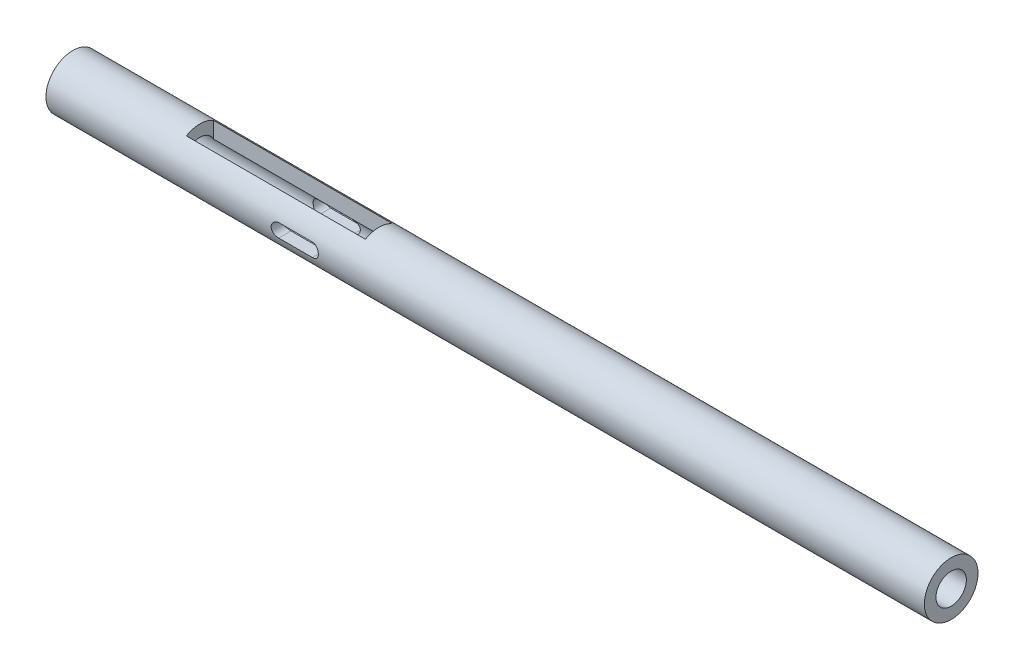
SolidWorks part; units mm, degrees
ref_plane "Front Plane" through (0, 0, 0) normal (0, 0, 1) x (1, 0, 0)
ref_plane "Top Plane" through (0, 0, 0) normal (0, 1, 0) x (1, 0, 0)
ref_plane "Right Plane" through (0, 0, 0) normal (1, 0, 0) x (0, 0, -1)
ref_axis "Axis1" through (105.6, 0, 0) along (-1, 0, 0)
sketch "Sketch2" plane through (0, 0, 0) normal (1, 0, 0) x (0, 0, -1)
  circle A0 centre (0, 0) radius 3.9688
  circle A1 centre (0, 0) radius 2.25
  dimension "D1" = 7.9375
  dimension "D2" = 4.5
extrude "Body" add sketch "Sketch2" along normal blind 130
sketch "Sketch4" plane through (0, 0, 0) normal (0, 1, 0) x (1, 0, 0)
  line L0 (32.0604, 2) -> (32.0604, -2) construction
  line L1 (18.8127, 2) -> (45.3081, 2)
  line L2 (18.8127, 2) -> (18.8127, -2)
  line L3 (18.8127, -2) -> (45.3081, -2)
  line L4 (45.3081, 2) -> (45.3081, -2)
  line L5 (105.6, 0) -> (-17.6, 0) construction
  line L6 (30.0865, 0) -> (43.0865, 0) construction
  point P7 (32.0604, 0)
  dimension "D1" = 4
extrude "cavity for slider" cut sketch "Sketch4" against normal through all and the other way through all
sketch "Sketch12" plane through (0, 0, 0) normal (0, 0, 1) x (1, 0, 0)
  line L0 (39.316, 0) -> (34.316, 0) construction
  line L1 (39.316, -0.9922) -> (34.316, -0.9922)
  line L2 (39.316, 0.9922) -> (34.316, 0.9922)
  arc A0 (39.316, -0.9922) -> (39.316, 0.9922) centre (39.316, 0) ccw
  arc A1 (34.316, 0.9922) -> (34.316, -0.9922) centre (34.316, 0) ccw
  point P2 (36.816, 0)
  point P8 (40.3081, 0)
  dimension "D1" = 0.9922
  dimension "D2" = 5
  dimension "D3" = 5
extrude "slider track for M2 screw 5/64 end mill" cut sketch "Sketch12" against normal through all both and the other way through all
sketch "Sketch5" [suppressed] plane through (0, 0, 0) normal (-1, 0, 0) x (0, 0, 1)
  circle A0 centre (0, 0) radius 3.9688
  dimension "D1" = 7.9375
extrude "Nose" [suppressed] add sketch "Sketch5" along normal blind 12
sketch "Sketch7" [suppressed] plane through (0, 0, 0) normal (0, 0, 1) x (1, 0, 0)
  line L0 (100, -3.9688) -> (99.9531, -3.9688)
  line L1 (99.9531, -3.9688) -> (99.9063, -3.5)
  line L2 (99.9063, -3.5) -> (99.8125, -3.5)
  line L3 (99.8125, -3.5) -> (99.8125, -6.698)
  line L4 (99.8125, -6.698) -> (100.1875, -6.698)
  line L5 (100.1875, -6.698) -> (100.1875, -3.5)
  line L6 (100.1875, -3.5) -> (100.0937, -3.5)
  line L7 (100.0937, -3.5) -> (100.0469, -3.9688)
  line L9 (100.0469, -3.9688) -> (100, -3.9688)
  line L10 (99.8125, -3.5) -> (99.8125, 0) construction
  line L11 (99.8125, 0) -> (100.1875, 0) construction
  line L12 (100.1875, 0) -> (100.1875, -3.5) construction
  line L13 (100, 0) -> (100, -3.9688) construction
  dimension "D1" = 3.5
  dimension "D2" = 0.0469
  dimension "D3" = 0.0938
  dimension "D4" = 0.1875
sketch "Sketch8" [suppressed] plane through (-12, 0, 0) normal (-1, 0, 0) x (0, 0, 1)
  circle A0 centre (0, 0) radius 3.9688 construction
  circle A1 centre (0, 0) radius 3.9688
curve "Helix/Spiral1" [suppressed] pitch 0.75 height 12 turns 16
chamfer "Chamfer1" [suppressed] distance 1 angle 45
sketch "Sketch10" [suppressed] plane through (-12, 0, 0) normal (-1, 0, 0) x (0, 0, 1)
  circle A0 centre (0, 0) radius 2.4
  dimension "D1" = 4.8
extrude "Cut-Extrude3" [suppressed] cut sketch "Sketch10" against normal through all contours A0
sweep "Cut-Sweep1" [suppressed] cut profiles "Sketch7" path "Helix/Spiral1"
sketch "Sketch3" [suppressed] plane through (0, 0, 0) normal (0, 0, 1) x (1, 0, 0)
  line L1 (28.2378, 0) -> (33.2378, 0) construction
  line L2 (28.2378, 0.9922) -> (33.2378, 0.9922)
  line L3 (28.2378, -0.9922) -> (33.2378, -0.9922)
  arc A0 (28.2378, 0.9922) -> (28.2378, -0.9922) centre (28.2378, 0) ccw
  arc A1 (33.2378, -0.9922) -> (33.2378, 0.9922) centre (33.2378, 0) ccw
  point P2 (30.7378, 0)
  point P9 (34.23, 0)
  dimension "D1" = 5
  dimension "D2" = 0.9922
  dimension "D3" = 3.77
extrude "slider track for shaft of shoulder screw (M2 screw 5/64\" end mill)" [suppressed] cut sketch "Sketch3" against normal through all and the other way through all
equation "\"Do\"=8.5mm"
equation "\"Lo\"=10"
equation "\"screw_diam\" = 3.5mm"
equation "\"wheel_Do\"=12.5mm"
equation "\"wheel_thickness\"=4mm"
equation "\"Collet_diameter\"=4.3"
equation "\"clearance\"= 0.5mm"
equation "\"D1@Sketch10\"=\"Collet_diameter\"+\"clearance\""
equation "\"handle_body_width\" = 10mm"
equation "\"finger_diameter\"=35"
equation "\"collet_lid_diameter\"=10"
equation "\"screw_cap_diam\"=5.15"
equation "\"handle_thickness\"=12.5mm"
equation "\"post_hole_diam\"=2"
equation "\"roll_rod_diam\"= 6.5 "
equation "\"roll_rod_length\"=6.6"
equation "\"disc_diam\"=5"
equation "\"disc_width\"=1.5"
equation "\"arm_width\"=5"
equation "\"arm_thickness\"=4.5"
equation "\"wheel_total_diam\"=30"
equation "\"spring_diam\"=4.1"
equation "\"collet_length\" = 18.75mm"
equation "\"D3@Sketch4\"=0.5*(\"wheel_Do\"*2+\"clearance\")-0.5mm"
